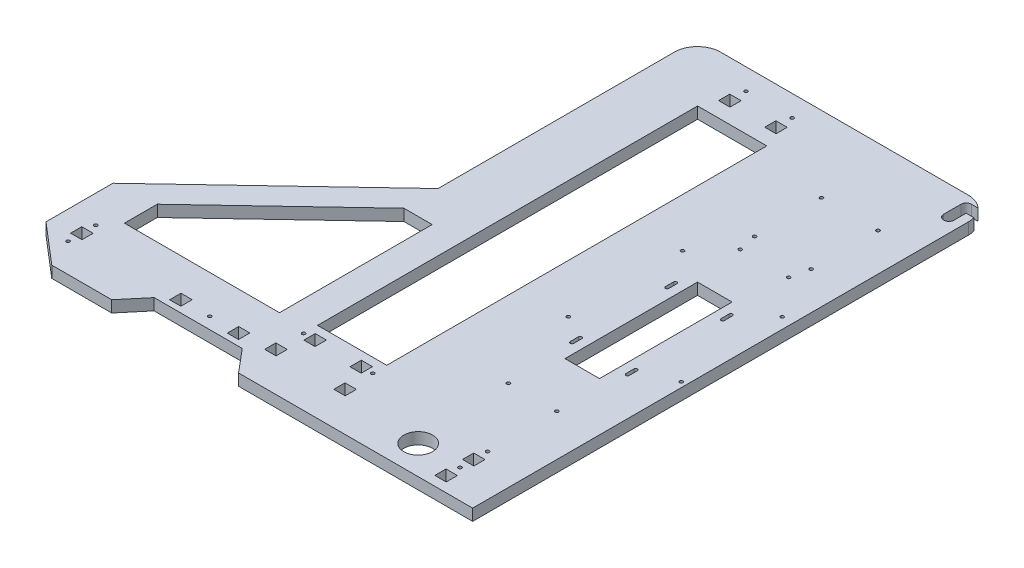
SolidWorks part; units mm, degrees
ref_plane "Front Plane" through (0, 0, 0) normal (0, 0, 1) x (1, 0, 0)
ref_plane "Top Plane" through (0, 0, 0) normal (0, 1, 0) x (1, 0, 0)
ref_plane "Right Plane" through (0, 0, 0) normal (1, 0, 0) x (0, 0, -1)
sketch "Sketch1" plane through (0, 0, 0) normal (0, 1, 0) x (1, 0, 0)
  line L0 (0, 0) -> (-235, 0)
  line L1 (-235, 0) -> (-235, -225)
  line L2 (-235, -225) -> (-380, -362)
  line L3 (-380, -362) -> (-380, -420)
  line L4 (-380, -420) -> (-345, -450)
  line L5 (-345, -450) -> (-293, -450)
  line L6 (-293, -450) -> (-263.6315, -415)
  line L7 (-263.6315, -415) -> (-212.3685, -415)
  line L8 (-212.3685, -415) -> (-183, -450)
  line L9 (-183, -450) -> (0, -450)
  line L10 (0, 0) -> (0, -450)
  line L12 (-293, -450) -> (-183, -450) construction
  dimension "D3" = 235
  dimension "D5" = 58
  dimension "D13" = 190
  dimension "D7" = 35
  dimension "D15" = 52
  dimension "D12" = 30
  dimension "D10" = 35
  dimension "D6" = 380
  dimension "D4" = 450
  dimension "D2" = 50
  dimension "D8" = 50
  dimension "D9" = 110
extrude "Boss-Extrude1" add sketch "Sketch1" along normal blind 10
sketch "Sketch16" plane through (0, 10, 0) normal (0, 1, 0) x (1, 0, 0)
  line L0 (0, -450) -> (20, -450)
  line L1 (20, -450) -> (20, 0)
  line L2 (20, 0) -> (0, 0)
  line L3 (0, 0) -> (0, -450)
  dimension "D1" = 20
  dimension "D2" = 90
extrude "Boss-Extrude2" add sketch "Sketch16" against normal through all
sketch "Sketch2" plane through (0, 10, 0) normal (0, 1, 0) x (1, 0, 0)
  line L0 (-235, -225) -> (-235, -415) construction
  line L1 (-263.6315, -415) -> (-212.3685, -415) construction
  line L2 (-345, -450) -> (-345, -328.931) construction
  line L3 (-235, -225) -> (-380, -362) construction
  line L4 (-345, -358.5097) -> (-235, -254.5787)
  line L5 (-235, -254.5787) -> (-210.5, -254.5787)
  line L6 (-210.5, -254.5787) -> (-210.5, -387)
  line L7 (-210.5, -387) -> (-345, -387)
  line L8 (-345, -387) -> (-345, -358.5097)
  line L9 (0, -450) -> (0, 0) construction
  line L10 (-184.5, -380) -> (-124.5, -380)
  line L11 (-184.5, -380) -> (-184.5, -50.425)
  line L12 (-184.5, -50.425) -> (-124.5, -50.425)
  line L13 (-124.5, -380) -> (-124.5, -50.425)
  line L14 (-124.5, -392.1) -> (-184.5, -392.1) construction
  line L15 (-16, -450) -> (-16, 0) construction
  line L16 (20, 0) -> (-235, 0) construction
  line L17 (-355.9, -440.6571) -> (-355.9, -339.2297) construction
  line L18 (-20.925, -441.85) -> (-11.075, -441.85)
  line L19 (-20.925, -441.85) -> (-20.925, -432.15)
  line L20 (-20.925, -432.15) -> (-11.075, -432.15)
  line L21 (-11.075, -441.85) -> (-11.075, -432.15)
  line L22 (-20.925, -441.85) -> (-11.075, -432.15) construction
  line L23 (-20.925, -432.15) -> (-11.075, -441.85) construction
  line L24 (-20.925, -417.85) -> (-11.075, -417.85)
  line L25 (-20.925, -417.85) -> (-20.925, -408.15)
  line L26 (-20.925, -408.15) -> (-11.075, -408.15)
  line L27 (-11.075, -417.85) -> (-11.075, -408.15)
  line L28 (-20.925, -417.85) -> (-11.075, -408.15) construction
  line L29 (-20.925, -408.15) -> (-11.075, -417.85) construction
  line L30 (-380, -420) -> (-345, -450) construction
  line L32 (-350.975, -408.15) -> (-360.825, -408.15)
  line L33 (-350.975, -408.15) -> (-350.975, -417.85)
  line L34 (-350.975, -417.85) -> (-360.825, -417.85)
  line L35 (-360.825, -408.15) -> (-360.825, -417.85)
  line L36 (-350.975, -408.15) -> (-360.825, -417.85) construction
  line L37 (-350.975, -417.85) -> (-360.825, -408.15) construction
  line L38 (-183, -450) -> (20, -450) construction
  line L39 (-183, -450) -> (20, -450) construction
  line L40 (-173.749, -32.425) -> (-113.749, -32.425) construction
  line L41 (-154.5, -50.425) -> (-154.5, -32.425) construction
  line L42 (-179.425, -27.575) -> (-169.575, -27.575)
  line L43 (-179.425, -27.575) -> (-179.425, -37.275)
  line L44 (-179.425, -37.275) -> (-169.575, -37.275)
  line L45 (-169.575, -27.575) -> (-169.575, -37.275)
  line L46 (-179.425, -27.575) -> (-169.575, -37.275) construction
  line L47 (-179.425, -37.275) -> (-169.575, -27.575) construction
  line L48 (-129.575, -37.275) -> (-139.425, -27.575) construction
  line L49 (-129.575, -27.575) -> (-139.425, -37.275) construction
  line L50 (-139.425, -27.575) -> (-139.425, -37.275)
  line L51 (-129.575, -37.275) -> (-139.425, -37.275)
  line L52 (-129.575, -27.575) -> (-129.575, -37.275)
  line L53 (-129.575, -27.575) -> (-139.425, -27.575)
  line L54 (-174.5, -32.425) -> (-174.5, -18.425) construction
  line L55 (-134.5, -32.425) -> (-134.5, -18.425) construction
  line L56 (-154.5, -380) -> (-154.5, -450) construction
  line L57 (-174.5, -392.1) -> (-134.5, -392.1) construction
  line L58 (-129.65, -397.025) -> (-139.35, -387.175) construction
  line L59 (-179.35, -387.175) -> (-169.65, -387.175)
  line L60 (-179.35, -387.175) -> (-179.35, -397.025)
  line L61 (-179.35, -397.025) -> (-169.65, -397.025)
  line L62 (-169.65, -387.175) -> (-169.65, -397.025)
  line L63 (-179.35, -387.175) -> (-169.65, -397.025) construction
  line L64 (-179.35, -397.025) -> (-169.65, -387.175) construction
  line L65 (-129.65, -387.175) -> (-139.35, -397.025) construction
  line L66 (-139.35, -387.175) -> (-139.35, -397.025)
  line L67 (-129.65, -397.025) -> (-139.35, -397.025)
  line L68 (-129.65, -387.175) -> (-129.65, -397.025)
  line L69 (-129.65, -387.175) -> (-139.35, -387.175)
  line L70 (-119.575, -420.95) -> (-129.425, -411.25) construction
  line L71 (-189.425, -411.25) -> (-179.575, -411.25)
  line L72 (-189.425, -411.25) -> (-189.425, -420.95)
  line L73 (-189.425, -420.95) -> (-179.575, -420.95)
  line L74 (-179.575, -411.25) -> (-179.575, -420.95)
  line L75 (-189.425, -411.25) -> (-179.575, -420.95) construction
  line L76 (-189.425, -420.95) -> (-179.575, -411.25) construction
  line L77 (-119.575, -411.25) -> (-129.425, -420.95) construction
  line L78 (-129.425, -411.25) -> (-129.425, -420.95)
  line L79 (-119.575, -420.95) -> (-129.425, -420.95)
  line L80 (-119.575, -411.25) -> (-119.575, -420.95)
  line L81 (-119.575, -411.25) -> (-129.425, -411.25)
  line L82 (-360.825, -408.15) -> (-11.075, -408.15) construction
  circle A0 centre (-16, -425) radius 1.45
  circle A1 centre (-16, -401) radius 1.45
  circle A2 centre (-355.9, -425) radius 1.45
  circle A3 centre (-355.9, -401) radius 1.45
  circle A4 centre (-174.5, -18.425) radius 1.45
  circle A5 centre (-134.5, -18.425) radius 1.45
  circle A6 centre (-124.5, -392.1) radius 1.45
  circle A7 centre (-184.5, -392.1) radius 1.45
  point P25 (-16, -437)
  point P30 (-16, -413)
  point P44 (-355.9, -413)
  point P61 (-174.5, -32.425)
  point P72 (-134.5, -32.425)
  point P85 (-174.5, -392.1)
  point P94 (-134.5, -392.1)
  point P95 (-184.5, -416.1)
  point P104 (-124.5, -416.1)
  point P105 (-154.5, -392.1)
  dimension "D13" = 2.9
  dimension "D14" = 2.9
  dimension "D23" = 2.9
  dimension "D24" = 2.9
  dimension "D31" = 2.9
  dimension "D37" = 2.9
  dimension "D1" = 21.5
  dimension "D2" = 28
  dimension "D3" = 24.5
  dimension "D4" = 60
  dimension "D7" = 26
  dimension "D8" = 9.7
  dimension "D9" = 9.85
  dimension "D10" = 9.85
  dimension "D11" = 9.7
  dimension "D12" = 24
  dimension "D15" = 24
  dimension "D19" = 9.85
  dimension "D20" = 9.7
  dimension "D26" = 12
  dimension "D27" = 9.85
  dimension "D28" = 9.7
  dimension "D33" = 9.7
  dimension "D38" = 9.85
  dimension "D39" = 9.7
  dimension "D41" = 24
  dimension "D34" = 30
  dimension "D36" = 12.1
  dimension "D30" = 18
  dimension "D29" = 40
  dimension "D17" = 13
  dimension "D32" = 14
  dimension "D35" = 20
  dimension "D16" = 12
  dimension "D21" = 90
  dimension "D25" = 24
  dimension "D5" = 359.75
  dimension "D22" = 349.75
  dimension "D40" = 30
  dimension "D6" = 70
  dimension "D42" = 0
  dimension "D43" = 0
  dimension "D18" = 16
  dimension "D44" = 9.85
extrude "Cut-Extrude1" cut sketch "Sketch2" against normal through all
fillet "Fillet1" radius 20 2 edges at (-235, 5, 0) (20, 5, 0)
sketch "Sketch11" plane through (0, 10, 0) normal (0, 1, 0) x (1, 0, 0)
  line L0 (-124.5, -215.2125) -> (20, -215.2125) construction
  line L1 (20, -450) -> (20, -20) construction
  line L3 (-52.25, -215.2125) -> (-52.25, -450) construction
  line L6 (-124.5, -380) -> (-124.5, -50.425) construction
  line L8 (-183, -450) -> (20, -450) construction
  circle A0 centre (-52.25, -425) radius 12.5
  circle A1 centre (-16, -425) radius 1.45 construction
  dimension "D1" = 25
  dimension "D2" = 0
  dimension "D3" = 0
extrude "WiringHole" cut sketch "Sketch11" against normal through all
sketch "Sketch9" [suppressed] plane through (0, 10, 0) normal (0, 1, 0) x (1, 0, 0)
  line L0 (-52.25, -412.5) -> (-52.25, 0) construction
  line L1 (0, 0) -> (-215, 0) construction
  line L2 (-124.5, -215.2125) -> (20, -215.2125) construction
  line L3 (-124.5, -380) -> (-124.5, -50.425) construction
  line L4 (-4.75, -126.7125) -> (-4.75, -303.7125) construction
  line L6 (-99.75, -126.7125) -> (-4.75, -126.7125) construction
  line L7 (-4.75, -303.7125) -> (-99.75, -303.7125) construction
  line L8 (-99.75, -303.7125) -> (-99.75, -126.7125) construction
  line L9 (20, -450) -> (20, -20) construction
  circle A0 centre (-52.25, -425) radius 12.5 construction
  circle A1 centre (-99.75, -126.7125) radius 1.45
  circle A2 centre (-4.75, -126.7125) radius 1.45
  circle A3 centre (-4.75, -303.7125) radius 1.45
  circle A4 centre (-99.75, -303.7125) radius 1.45
  dimension "D3" = 2.9
  dimension "D4" = 2.9
  dimension "D1" = 95
  dimension "D2" = 177
  dimension "D5" = 47.5
extrude "MountingHoles-PSU" [suppressed] cut sketch "Sketch9" against normal through all
sketch "Sketch10" plane through (0, 10, 0) normal (0, 1, 0) x (1, 0, 0)
  line L0 (-124.5, -215.2125) -> (20, -215.2125) construction
  line L1 (20, -450) -> (20, -20) construction
  line L2 (-52.25, -240.2125) -> (-22.25, -240.2125) construction
  line L3 (-37.25, -210.225) -> (-37.25, 0) construction
  line L4 (-52.25, -215.2125) -> (-52.25, -184.5972) construction
  line L7 (-124.5, -380) -> (-124.5, -50.425) construction
  line L8 (-52.25, -297.7125) -> (-22.25, -297.7125)
  line L9 (-52.25, -297.7125) -> (-52.25, -182.7125)
  line L10 (-52.25, -182.7125) -> (-22.25, -182.7125)
  line L11 (-22.25, -297.7125) -> (-22.25, -182.7125)
  line L12 (-52.25, -297.7125) -> (-22.25, -182.7125) construction
  line L13 (-52.25, -182.7125) -> (-22.25, -297.7125) construction
  line L15 (0, 0) -> (-215, 0) construction
  line L17 (-37.25, -210.225) -> (-37.25, -450) construction
  line L18 (-183, -450) -> (20, -450) construction
  line L19 (-64.75, -215.2125) -> (-39.75, -215.2125) construction
  line L20 (-37.25, -297.7125) -> (-37.25, -182.7125) construction
  dimension "D1" = 30
  dimension "D2" = 115
  dimension "D3" = 0
  dimension "D4" = 0
  dimension "D5" = 0
  dimension "D6" = 25
  dimension "D7" = 15
extrude "WiringSlot" cut sketch "Sketch10" against normal through all
sketch "CenterLines" plane through (0, 10, 0) normal (0, 1, 0) x (1, 0, 0)
  line L0 (-37.25, -297.7125) -> (-37.25, -182.7125) construction
  line L1 (-52.25, -297.7125) -> (-22.25, -297.7125) construction
  line L2 (-22.25, -182.7125) -> (-52.25, -182.7125) construction
  line L3 (-52.25, -240.2125) -> (-22.25, -240.2125) construction
  line L4 (-52.25, -182.7125) -> (-52.25, -297.7125) construction
  line L5 (-22.25, -297.7125) -> (-22.25, -182.7125) construction
ref_plane "Plane1" through (-37.25, 0, 0) normal (1, 0, 0) x (0, 0, -1)
sketch "Sketch6" plane through (0, 10, 0) normal (0, 1, 0) x (1, 0, 0)
  line L0 (-37.25, -297.7125) -> (-37.25, -182.7125) construction
  line L1 (-61.35, -237.7125) -> (-13.15, -237.7125) construction
  line L2 (-13.15, -192.9625) -> (-13.15, -275.4625) construction
  line L3 (-52.25, -297.7125) -> (-22.25, -297.7125) construction
  line L4 (-52.25, -235.2125) -> (-22.25, -235.2125) construction
  line L5 (-22.25, -182.7125) -> (-52.25, -182.7125) construction
  line L6 (-13.15, -192.9625) -> (-13.15, -199.9625) construction
  line L7 (-11.7, -192.9625) -> (-11.7, -199.9625)
  line L8 (-14.6, -192.9625) -> (-14.6, -199.9625)
  line L9 (-52.25, -240.2125) -> (-22.25, -240.2125) construction
  line L10 (-52.25, -182.7125) -> (-52.25, -297.7125) construction
  line L11 (-22.25, -297.7125) -> (-22.25, -182.7125) construction
  line L12 (-13.15, -282.4625) -> (-13.15, -275.4625) construction
  line L13 (-14.6, -282.4625) -> (-14.6, -275.4625)
  line L14 (-61.35, -275.4625) -> (-61.35, -199.9625) construction
  line L15 (-13.15, -282.4625) -> (-13.15, -199.9625) construction
  line L16 (-11.7, -282.4625) -> (-11.7, -275.4625)
  arc A2 (-11.7, -192.9625) -> (-14.6, -192.9625) centre (-13.15, -192.9625) ccw
  arc A3 (-14.6, -199.9625) -> (-11.7, -199.9625) centre (-13.15, -199.9625) ccw
  circle A4 centre (-61.35, -275.4625) radius 1.45
  circle A6 centre (-61.35, -199.9625) radius 1.45
  arc A8 (-14.6, -282.4625) -> (-11.7, -282.4625) centre (-13.15, -282.4625) ccw
  arc A9 (-11.7, -275.4625) -> (-14.6, -275.4625) centre (-13.15, -275.4625) ccw
  point P20 (-13.15, -196.4625)
  point P25 (-13.15, -278.9625)
  dimension "D8" = 2.9
  dimension "D12" = 2.9
  dimension "D4" = 1.45
  dimension "D5" = 1.45
  dimension "D11" = 82.5
  dimension "D14" = 75.5
  dimension "D2" = 24.1
  dimension "D3" = 48.2
  dimension "D6" = 2.5
  dimension "D9" = 7
  dimension "D10" = 7
extrude "MountingHoles-RAMPS" cut sketch "Sketch6" against normal through all
mirror "Mirror1" about plane through (-37.25, 0, 0) normal (1, 0, 0) of "MountingHoles-RAMPS"
sketch "Sketch5" plane through (0, 10, 0) normal (0, 1, 0) x (1, 0, 0)
  line L0 (-22.25, -240.2125) -> (-52.25, -240.2125) construction
  line L3 (-22.25, -297.7125) -> (-22.25, -182.7125) construction
  line L5 (-52.25, -182.7125) -> (-52.25, -297.7125) construction
  line L7 (-16.25, -139.7125) -> (-58.25, -139.7125) construction
  line L8 (-16.25, -340.7125) -> (-58.25, -340.7125) construction
  line L9 (-37.25, -240.2125) -> (-37.25, -139.7125) construction
  line L10 (-37.25, -240.2125) -> (-37.25, -340.7125) construction
  circle A0 centre (-58.25, -139.7125) radius 1.45
  circle A1 centre (-16.25, -139.7125) radius 1.45
  circle A2 centre (-16.25, -340.7125) radius 1.45
  circle A3 centre (-58.25, -340.7125) radius 1.45
  point P17 (-37.25, -139.7125)
  point P22 (-37.25, -340.7125)
  dimension "D2" = 2.9
  dimension "D5" = 2.9
  dimension "D6" = 2.9
  dimension "D7" = 2.9
  dimension "D3" = 201
  dimension "D4" = 100.5
  dimension "D8" = 21
  dimension "D9" = 21
  dimension "D10" = 100.5
extrude "MountingHoles-Melzi" cut sketch "Sketch5" against normal through all
sketch "Sketch13" plane through (0, 0, 0) normal (0, -1, 0) x (-1, 0, 0)
  line L0 (52.25, -215.2125) -> (124.5, -215.2125) construction
  line L1 (124.5, -380) -> (124.5, -50.425) construction
  line L2 (82.25, -264.7275) -> (82.25, -165.6975) construction
  line L3 (37.25, -297.7125) -> (37.25, -182.7125) construction
  line L4 (52.25, -182.7125) -> (52.25, -297.7125) construction
  line L6 (82.25, -264.7275) -> (-15.65, -264.7275) construction
  circle A0 centre (82.25, -165.6975) radius 1.45
  circle A1 centre (82.25, -264.7275) radius 1.45
  circle A2 centre (-10.59, -172.1775) radius 1.45
  circle A3 centre (-15.65, -264.7275) radius 1.45
  point P11 (82.25, -215.2125)
  dimension "D8" = 2.9
  dimension "D6" = 2.9
  dimension "D1" = 2.9
  dimension "D2" = 49.515
  dimension "D3" = 45
  dimension "D4" = 6.48
  dimension "D5" = 92.84
  dimension "D7" = 97.9
extrude "Mountingholes-Smoothieboard" cut sketch "Sketch13" against normal through all
mirror "Flipped" [suppressed] about plane through (-37.25, 0, 0) normal (1, 0, 0)
sketch "Sketch21" plane through (0, 10, 0) normal (0, 1, 0) x (1, 0, 0)
  line L0 (-37.25, -182.7125) -> (-37.25, 0) construction
  line L1 (-22.25, -182.7125) -> (-52.25, -182.7125) construction
  line L2 (0, 0) -> (-215, 0) construction
  line L3 (-37.25, -94.7125) -> (-23.3697, -94.7125) construction
  circle A0 centre (-12.75, -65.7125) radius 1.45
  circle A1 centre (-61.75, -65.7125) radius 1.45
  circle A2 centre (-61.75, -123.7125) radius 1.45
  circle A3 centre (-12.75, -123.7125) radius 1.45
  circle A4 centre (-16.25, -139.7125) radius 1.45 construction
  dimension "D1" = 2.9
  dimension "D2" = 24.5
  dimension "D3" = 29
  dimension "D4" = 45
extrude "Pi" cut sketch "Sketch21" against normal through all
sketch "Sketch17" plane through (0, 10, 0) normal (0, 1, 0) x (1, 0, 0)
  line L0 (0, 0) -> (20, 0) construction
  line L1 (20, -23.6361) -> (20, 0) construction
  line L2 (20, -450) -> (20, -20) construction
  line L3 (20, -10) -> (8, -10) construction
  line L4 (20, -14.5) -> (8, -14.5)
  line L5 (20, -5.5) -> (8, -5.5)
  arc A0 (20, -14.5) -> (20, -5.5) centre (20, -10) ccw
  arc A1 (8, -5.5) -> (8, -14.5) centre (8, -10) ccw
  point P8 (14, -10)
  dimension "D1" = 9
  dimension "D2" = 12
  dimension "D3" = 10
extrude "Cut-Extrude3" cut sketch "Sketch17" against normal through all
sketch "Sketch18" plane through (0, 10, 0) normal (0, 1, 0) x (1, 0, 0)
  line L0 (8, -5.5) -> (8, -14.5) construction
  line L1 (3.5, -10) -> (8, -10) construction
  line L2 (8, -10) -> (8, -25) construction
  line L3 (12.5, -10) -> (12.5, -25)
  line L4 (3.5, -10) -> (3.5, -25)
  arc A0 (8, -5.5) -> (8, -14.5) centre (8, -10) ccw construction
  arc A1 (12.5, -10) -> (3.5, -10) centre (8, -10) ccw
  arc A2 (3.5, -25) -> (12.5, -25) centre (8, -25) ccw
  point P10 (8, -17.5)
  dimension "D1" = 9
  dimension "D2" = 0
  dimension "D3" = 15
extrude "Cut-Extrude4" cut sketch "Sketch18" against normal through all
sketch "Sketch19" plane through (0, 10, 0) normal (0, 1, 0) x (1, 0, 0)
  line L0 (-2, -25) -> (18, -25) construction
  line L1 (8, -25) -> (8, -5.5) construction
  circle A0 centre (18, -25) radius 1.45
  arc A1 (8, -5.5) -> (3.5, -10) centre (8, -10) ccw construction
  circle A2 centre (-2, -25) radius 1.45
  dimension "D2" = 2.9
extrude "Cut-Extrude5" [suppressed] cut sketch "Sketch19" against normal through all
sketch "Sketch22" plane through (0, 10, 0) normal (0, 1, 0) x (1, 0, 0)
  line L0 (-276.218, -430) -> (-199.782, -430)
  line L1 (-293, -450) -> (-263.6315, -415) construction
  line L2 (-212.3685, -415) -> (-183, -450) construction
  line L3 (-199.782, -430) -> (-212.3685, -415)
  line L4 (-212.3685, -415) -> (-263.6315, -415)
  line L5 (-263.6315, -415) -> (-276.218, -430)
  dimension "D1" = 15
extrude "Boss-Extrude3" add sketch "Sketch22" against normal through all
sketch "Sketch23" plane through (0, 10, 0) normal (0, 1, 0) x (1, 0, 0)
  line L0 (-238, -430) -> (-238, -387) construction
  line L1 (-276.218, -430) -> (-199.782, -430) construction
  line L2 (-345, -387) -> (-210.5, -387) construction
  line L3 (-213, -420) -> (-263, -420) construction
  line L4 (-179.35, -387.175) -> (-179.35, -397.025) construction
  line L5 (-267.85, -415.075) -> (-258.15, -415.075)
  line L6 (-267.85, -415.075) -> (-267.85, -424.925)
  line L7 (-267.85, -424.925) -> (-258.15, -424.925)
  line L8 (-258.15, -415.075) -> (-258.15, -424.925)
  line L9 (-267.85, -415.075) -> (-258.15, -424.925) construction
  line L10 (-267.85, -424.925) -> (-258.15, -415.075) construction
  line L11 (-208.15, -424.925) -> (-217.85, -415.075) construction
  line L12 (-208.15, -415.075) -> (-217.85, -424.925) construction
  line L13 (-217.85, -415.075) -> (-217.85, -424.925)
  line L14 (-208.15, -424.925) -> (-217.85, -424.925)
  line L15 (-208.15, -415.075) -> (-208.15, -424.925)
  line L16 (-208.15, -415.075) -> (-217.85, -415.075)
  circle A0 centre (-238, -420) radius 1.45
  point P19 (-238, -420)
  dimension "D4" = 2.9
  dimension "D1" = 9.7
  dimension "D3" = 10
extrude "Cut-Extrude6" cut sketch "Sketch23" against normal through all
equation "\"Y-ROD-SPACING\"=75"
equation "\"Y-BED-OFFSET\"=2"
equation "\"Y-BED-ROD-INSET\"=3.5"
equation "\"T-SLOT-NUT-FILLET-RADIUS\"=0.5"
equation "\"T-SLOT-SCREW-SHAFT-RADIUS\"=1.55"
equation "\"T-SLOT-SCREW-SHAFT-CUTOUT-LENGTH\"=11"
equation "\"T-SLOT-NUT-DEPTH\"=3.5"
equation "\"T-SLOT-NUT-WIDTH\"=2.85"
equation "\"T-SLOT-NUT-END-DISTANCE\"=8"
equation "\"ACRYLIC-TAB-CUTOUT-SIZE\"=\"ACRYLIC-THICKNESS\"+\"ACRYLIC-TAB-TOLERANCE\"*2"
equation "\"ACRYLIC-TAB-WIDTH\"=\"ACRYLIC-THICKNESS\""
equation "\"ACRYLIC-M3-HOLE\"=2.9"
equation "\"SMOOTHROD-CAP-SCREW-DISTANCE\"=20"
equation "\"FRAME-WIDTH-INNER\"=370"
equation "\"D24@Sketch2\"=\"ACRYLIC-M3-HOLE\""
equation "\"D23@Sketch2\"=\"ACRYLIC-M3-HOLE\""
equation "\"D19@Sketch2\"=\"ACRYLIC-THICKNESS\"-\"KERF\"*2"
equation "\"D20@Sketch2\"=\"ACRYLIC-TAB-WIDTH\"-\"KERF\"*4"
equation "\"D37@Sketch2\"=\"ACRYLIC-M3-HOLE\""
equation "\"D33@Sketch2\"=\"ACRYLIC-TAB-WIDTH\"-\"KERF\"*4"
equation "\"D38@Sketch2\"=\"ACRYLIC-THICKNESS\"-\"KERF\"*2"
equation "\"D39@Sketch2\"=\"ACRYLIC-TAB-WIDTH\"-\"KERF\"*4"
equation "\"D13@Sketch2\"=\"ACRYLIC-M3-HOLE\""
equation "\"D14@Sketch2\"=\"ACRYLIC-M3-HOLE\""
equation "\"D8@Sketch2\"=\"ACRYLIC-TAB-WIDTH\"-\"KERF\"*4"
equation "\"D9@Sketch2\"=\"ACRYLIC-THICKNESS\"-\"KERF\"*2"
equation "\"D10@Sketch2\"=\"ACRYLIC-THICKNESS\"-\"KERF\"*2"
equation "\"D11@Sketch2\"=\"ACRYLIC-TAB-WIDTH\"-\"KERF\"*4"
equation "\"D31@Sketch2\"=\"ACRYLIC-M3-HOLE\""
equation "\"D27@Sketch2\"=\"ACRYLIC-THICKNESS\"-\"KERF\"*2"
equation "\"D28@Sketch2\"=\"ACRYLIC-TAB-WIDTH\"-\"KERF\"*4"
equation "\"NEMA17-HOLE-SPACING\"=31"
equation "\"NEMA17-CENTRAL-CUTOUT\"=22.5"
equation "\"Z-BRACKET-REACH\"=57"
equation "\"TOP-BRACKET-SPACING\"=40"
equation "\"D29@Sketch2\"=\"TOP-BRACKET-SPACING\""
equation "\"ACRYLIC-THICKNESS\"=10"
equation "\"SMOOTHROD-Z-LENGTH\"=350"
equation "\"D5@Sketch2\"=\"SMOOTHROD-Z-LENGTH\"-\"SMOOTHROD-TIGHTENING-HEADROOM\"+10"
equation "\"SMOOTHROD-X-LENGTH\"=350"
equation "\"SMOOTHROD-Y-LENGTH\"=350"
equation "\"D22@Sketch2\"=\"SMOOTHROD-Y-LENGTH\"-\"SMOOTHROD-TIGHTENING-HEADROOM\""
equation "\"SMOOTHROD-TIGHTENING-HEADROOM\"=.25"
equation "\"X-ROD-SPACING\"=45"
equation "\"Z-ROD-SPACING\"=17.5"
equation "\"LEADSCREW-Z-LENGTH\"=300"
equation "\"SCREW-HEAD-RADIUS\"=6"
equation "\"PRINTED-X-SMOOTHROD-DIAMETER\"=8.8"
equation "\"PRINTED-X-SMOOTHROD-CUTOUT\"=10"
equation "\"PRINTED-X-BASE-HEIGHT\"=10"
equation "\"PRINTED-LM8UU-CUTOUT-SIZE\"=15.5"
equation "\"PRINTED-LM8UU-CUTOUT-LENGTH\"=24.5"
equation "\"PRINTED-X-IDLER-HEIGHT\"=16"
equation "\"PSU-MOUNTING-WIDTH\"=95"
equation "\"PSU-MOUNTING-HEIGHT\"=177"
equation "\"D1@Sketch9\"=\"PSU-MOUNTING-WIDTH\""
equation "\"D3@Sketch9\"=\"ACRYLIC-M3-HOLE\""
equation "\"D1@Boss-Extrude1\"=\"ACRYLIC-THICKNESS\""
equation "\"D6@Sketch1\"=\"SMOOTHROD-Y-LENGTH\"+30"
equation "\"D4@Sketch9\"=\"ACRYLIC-M3-HOLE\""
equation "\"D2@Sketch9\"=\"PSU-MOUNTING-HEIGHT\""
equation "\"D5@Sketch9\"=\"PSU-MOUNTING-WIDTH\"/2"
equation "\"D4@Sketch1\"=\"SMOOTHROD-Z-LENGTH\"+100"
equation "\"D8@Sketch6\"=\"ACRYLIC-M3-HOLE\""
equation "\"D12@Sketch6\"=\"ACRYLIC-M3-HOLE\""
equation "\"D2@Sketch5\"=\"ACRYLIC-M3-HOLE\""
equation "\"D5@Sketch5\"=\"ACRYLIC-M3-HOLE\""
equation "\"D6@Sketch5\"=\"ACRYLIC-M3-HOLE\""
equation "\"D7@Sketch5\"=\"ACRYLIC-M3-HOLE\""
equation "\"D1@Sketch13\"=\"ACRYLIC-M3-HOLE\""
equation "\"D6@Sketch13\"=\"ACRYLIC-M3-HOLE\""
equation "\"D8@Sketch13\"=\"ACRYLIC-M3-HOLE\""
equation "\"D4@Sketch6\"=\"ACRYLIC-M3-HOLE\"/2"
equation "\"D5@Sketch6\"=\"ACRYLIC-M3-HOLE\"/2"
equation "\"Y-BED-SCREW-SPACING\"=209"
equation "\"Y-BED-SCREW-CUTOUT-SLOT-HEIGHT\"=2.5"
equation "\"ACRYLIC-THICKNESS2\"=4.5"
equation "\"ACRYLIC-TAB-TOLERANCE\"=-.05"
equation "\"Z-ROD-INSET\"=13.5"
equation "\"SCREW-LENGTH-FRAME\"=\"ACRYLIC-THICKNESS\" + 10"
equation "\"SCREW-LENGTH-MOTOR\"=\"ACRYLIC-THICKNESS\" + 5"
equation "\"SCREW-LENGTH-EXTRUDER\"=28"
equation "\"Y-BELT-TO-ROD-DISTANCE\"=20"
equation "\"SPOOL-HOLDER-ROD-SPACING\"=150"
equation "\"ACRYLIC-X-CARRIAGE-WIDTH\"=55"
equation "\"ACRYLIC-X-CARRIAGE-HEIGHT\"=75"
equation "\"ACRYLIC-X-CARRIAGE-LM8UU-CUTOUT-WIDTH\"=24.25"
equation "\"ACRYLIC-X-CARRIAGE-SCREW-SPACING-X\"=15"
equation "\"ACRYLIC-X-CARRIAGE-SCREW-SPACING-Y\"=33"
equation "\"ACRYLIC-X-CARRIAGE-CENTER-TAB-SPACING\"=14"
equation "\"ACRYLIC-X-CARRIAGE-EXTRUDER-OFFSET\"=26"
equation "\"ACRYLIC-X-CARRIAGE-EXTRUDER-ANGLE\"=90"
equation "\"ACRYLIC-X-CARRIAGE-EXTRUDER-SHELF-DEPTH\"=\"ACRYLIC-X-CARRIAGE-EXTRUDER-OFFSET\" + 28"
equation "\"ACRYLIC-X-CARRIAGE-EXTRUDER-BRACE-SPACING\"=23"
equation "\"ACRYLIC-X-CARRIAGE-EXTRUDER-BRACE-TAB-OFFSET\"=20"
equation "\"ACRYLIC-X-CARRIAGE-EXTRUDER-BRACE-HEIGHT\"=35"
equation "\"ACRYLIC-X-CARRIAGE-EXTRUDER-BRACE-SCREW-SPACING\"=22"
equation "\"D1@Sketch19\"=\"SMOOTHROD-CAP-SCREW-DISTANCE\"/2"
equation "\"D2@Sketch19\"=\"ACRYLIC-M3-HOLE\""
equation "\"D1@Sketch21\"=\"ACRYLIC-M3-HOLE\""
equation "\"KERF\"=0.075"
equation "\"PRINTED-M3-HOLE\"=3.5"
equation "\"PRINTED-M3-NUT-AF\"=6.25"
equation "\"ACRYLIC-X-CARRIAGE-LM8UU-CUTOUT-HEIGHT\"=11.0"
equation "\"ACRYLIC-X-CARRIAGE-DUAL-WIDTH-MULTIPLIER\"=1.65"
equation "\"ACRYLIC-X-CARRIAGE-DUAL-HOTEND-SPACING\"=42"
equation "\"ACRYLIC-X-CARRIAGE-DUAL-WIDTH\"=75"
equation "\"ACRYLIC-X-CARRIAGE-DUAL-FAN-OFFSET\"=52"
equation "\"ACRYLIC-X-CARRIAGE-DUAL-FAN-HEIGHT\"=20"
equation "\"ACRYLIC-X-CARRIAGE-DUAL-HOTEND-SEPARATION\"=36"
equation "\"ACRYLIC-X-CARRIAGE-DUAL-MOUNT-PLATE-DEPTH\"=75"
equation "\"ACRYLIC-X-CARRIAGE-DUAL-MOUNT-BRACE-WIDTH\"=33"
equation "\"ACRYLIC-X-CARRIAGE-DUAL-MOUNT-SCREW-WIDTH\"=40"
equation "\"BLOWER-FAN-WIDTH\"=15"
equation "\"D44@Sketch2\"=\"ACRYLIC-THICKNESS\"-\"KERF\"*2"
equation "\"D1@Sketch23\"=10-\"KERF\"*4"
equation "\"D4@Sketch23\"=\"ACRYLIC-M3-HOLE\""
